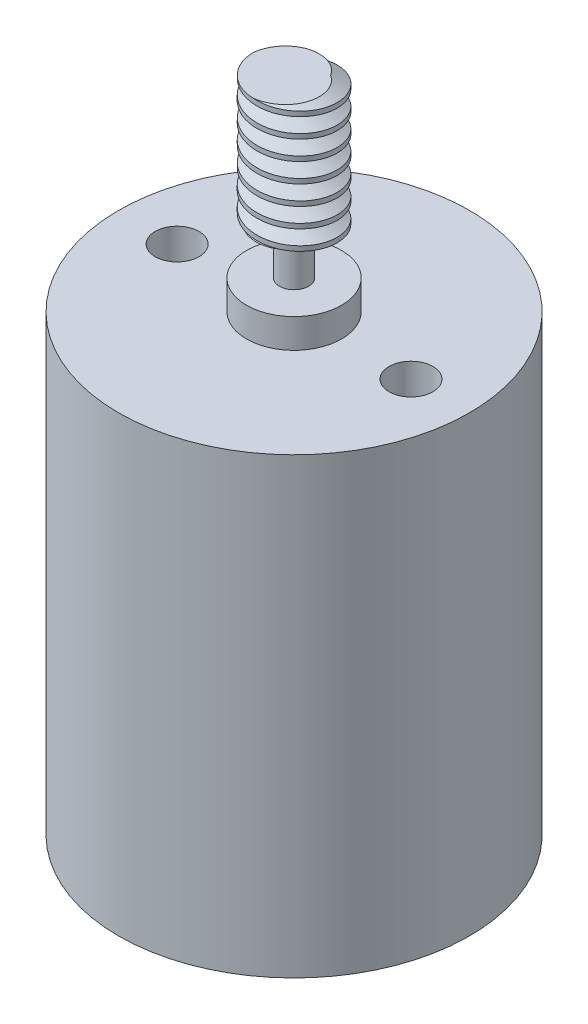
SolidWorks part; units mm, degrees
ref_plane "Front Plane" through (0, 0, 0) normal (0, 0, 1) x (1, 0, 0)
ref_plane "Top Plane" through (0, 0, 0) normal (0, 1, 0) x (1, 0, 0)
ref_plane "Right Plane" through (0, 0, 0) normal (1, 0, 0) x (0, 0, -1)
sketch "Sketch1" plane through (0, 0, 0) normal (0, 1, 0) x (1, 0, 0)
  circle A0 centre (0, 0) radius 12
  dimension "D1" = 24
extrude "Boss-Extrude1" add sketch "Sketch1" along normal blind 31
sketch "Sketch2" plane through (0, 31, 0) normal (0, 1, 0) x (1, 0, 0)
  circle A0 centre (8, 0) radius 1.5
  circle A1 centre (-8, 0) radius 1.5
  dimension "D1" = 3
  dimension "D2" = 3
  dimension "D3" = 16
  dimension "D4" = 8
extrude "Cut-Extrude1" cut sketch "Sketch2" against normal blind 5
sketch "Sketch3" plane through (0, 31, 0) normal (0, 1, 0) x (1, 0, 0)
  circle A0 centre (0, 0) radius 3.25
  dimension "D1" = 6.5
extrude "Boss-Extrude2" add sketch "Sketch3" along normal blind 2
sketch "Sketch4" plane through (0, 33, 0) normal (0, 1, 0) x (1, 0, 0)
  circle A0 centre (0, 0) radius 1
  dimension "D1" = 2
extrude "Boss-Extrude3" add sketch "Sketch4" along normal blind 12
sketch "Sketch5" plane through (0, 45, 0) normal (0, 1, 0) x (1, 0, 0)
  circle A0 centre (0, 0) radius 2.75
  dimension "D1" = 5.5
extrude "Boss-Extrude4" add sketch "Sketch5" against normal blind 9
sketch "Sketch8" plane through (0, 45, 0) normal (0, 1, 0) x (1, 0, 0)
  circle A0 centre (0, 0) radius 2.75
curve "Helix/Spiral1" pitch 1.33 height 1.33 turns 1
sketch "Sketch10" plane through (0, 45, 0) normal (0, 1, 0) x (1, 0, 0)
  circle A1 centre (0, 0) radius 2.75
curve "Helix/Spiral2" pitch 1.33 height 10.64 radius 2.75 left hand yes centre (0, 45, 0) axis (0, -1, 0) start towards (0, 0, 1)
sketch "Sketch6" plane through (0, 0, 0) normal (0, 0, 1) x (1, 0, 0)
  line L0 (-2.75, 45) -> (-1.7665, 44.5)
  line L1 (-1.7665, 44.5) -> (-2.75, 44)
  line L2 (-2.75, 45) -> (-2.75, 36) construction
  line L3 (-2.75, 44) -> (-2.75, 45)
  line L4 (0, 45) -> (0, 36) construction
  line L5 (2.75, 45) -> (-2.75, 45) construction
  line L6 (-1, 36) -> (1, 36) construction
  dimension "D1" = 1
  dimension "D2" = 0.5
sweep "Cut-Sweep6" cut profiles "Sketch6" path "Helix/Spiral2" align with end faces yes
equation "\"D2@Sketch2\"=\"D1@Sketch2\""
equation "\"D3@Sketch2\"=19-\"D2@Sketch2\""
equation "\"D4@Sketch2\"=\"D3@Sketch2\"/2"
equation "\"D2@Sketch6\"=\"D1@Sketch6\"/2"
